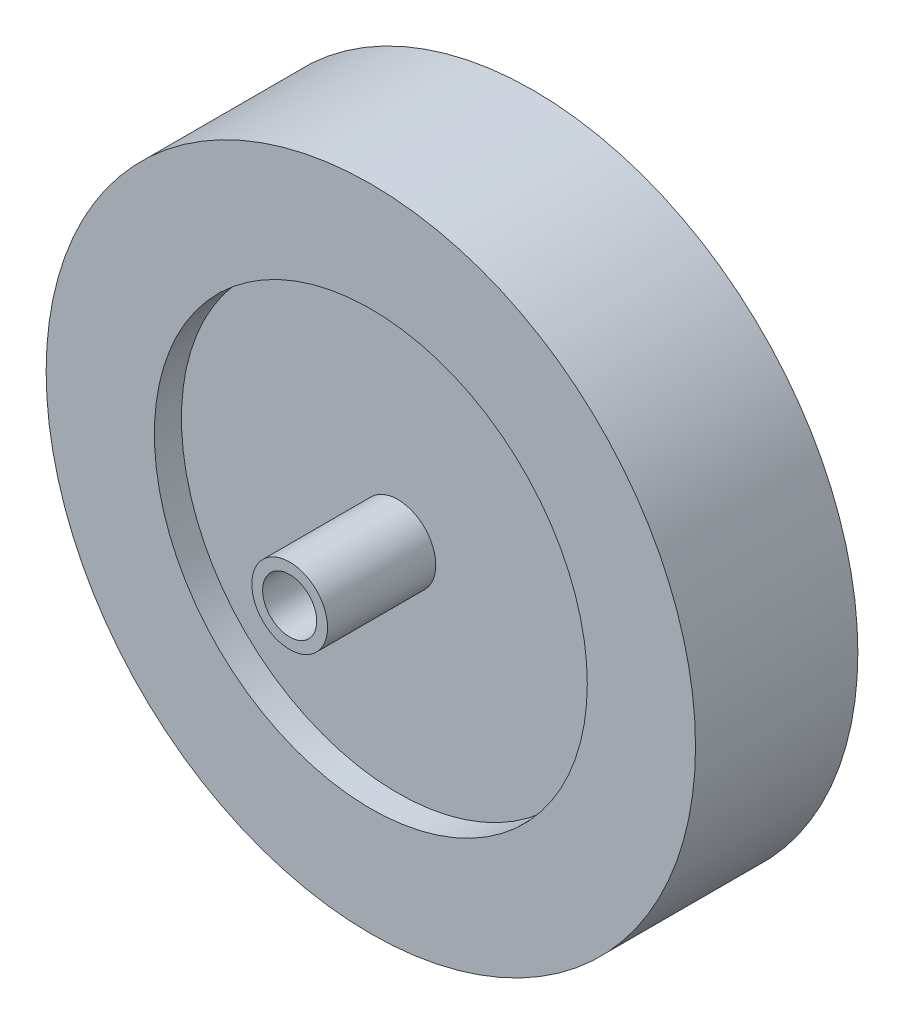
SolidWorks part; units mm, degrees
ref_plane "Front Plane" through (0, 0, 0) normal (0, 0, 1) x (1, 0, 0)
ref_plane "Top Plane" through (0, 0, 0) normal (0, 1, 0) x (1, 0, 0)
ref_plane "Right Plane" through (0, 0, 0) normal (1, 0, 0) x (0, 0, -1)
sketch "Sketch1" plane through (0, 0, 0) normal (0, 0, 1) x (1, 0, 0)
  circle A0 centre (0, 0) radius 60
  circle A1 centre (0, 0) radius 40
  circle A2 centre (0, 0) radius 7
  circle A3 centre (0, 0) radius 5
extrude "Boss-Extrude1" add sketch "Sketch1" along normal blind 15 and the other way blind 15 contours A0 A1 region at (-58.3029, 0, 0)
extrude "Boss-Extrude2" add sketch "Sketch1<3>" along normal blind 10 and the other way blind 10 separate body contours A1 A2 region at (-38.8686, 0, 0)
sketch "Sketch1<3>" plane through (0, 0, 0) normal (0, 0, 1) x (1, 0, 0) same geometry as "Sketch1"
extrude "Boss-Extrude3" add sketch "Sketch1<4>" along normal blind 30 separate body contours A2 A3 region at (-6.802, 0, 0)
sketch "Sketch1<4>" plane through (0, 0, 0) normal (0, 0, 1) x (1, 0, 0) same geometry as "Sketch1"
